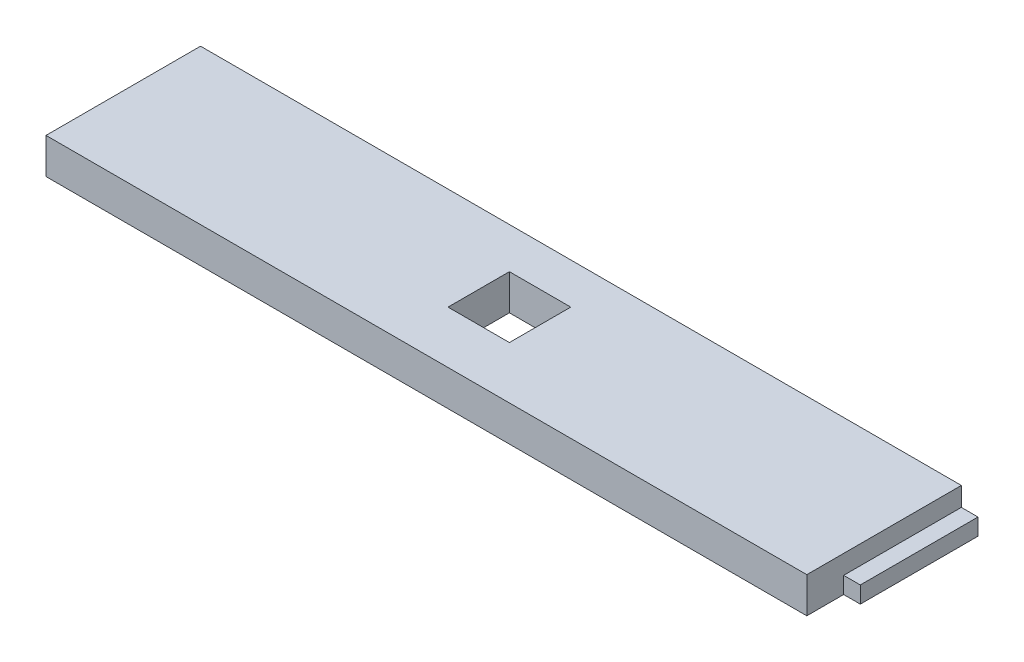
SolidWorks part; units mm, degrees
ref_plane "Front Plane" through (0, 0, 0) normal (0, 0, 1) x (1, 0, 0)
ref_plane "Top Plane" through (0, 0, 0) normal (0, 1, 0) x (1, 0, 0)
ref_plane "Right Plane" through (0, 0, 0) normal (1, 0, 0) x (0, 0, -1)
sketch "Sketch2" plane through (0, 0, 0) normal (0, 1, 0) x (1, 0, 0)
  line L0 (0, 65) -> (0, -65) construction
  line L1 (-350, -65) -> (350, -65)
  line L2 (-350, -65) -> (-350, 65)
  line L3 (-350, 65) -> (350, 65)
  line L4 (350, -65) -> (350, 65)
  line L5 (-350, -65) -> (350, 65) construction
  line L6 (-350, 65) -> (350, -65) construction
  line L7 (-320, 65) -> (-320, -65)
  line L8 (-25.815, -21) -> (25.815, -21)
  line L9 (-25.815, -21) -> (-25.815, 30.63)
  line L10 (-25.815, 30.63) -> (25.815, 30.63)
  line L11 (25.815, -21) -> (25.815, 30.63)
  line L12 (-25.815, -21) -> (25.815, 30.63) construction
  line L13 (-25.815, 30.63) -> (25.815, -21) construction
  line L14 (320, 65) -> (320, -65)
  line L15 (320, -34) -> (334, -34)
  line L16 (-315, -54.66) -> (315, -54.66)
  line L17 (-315, -54.66) -> (-315, -48.46)
  line L18 (-315, -48.46) -> (315, -48.46)
  line L19 (315, -54.66) -> (315, -48.46)
  line L20 (-320, 65) -> (-334, 65)
  line L21 (-320, 65) -> (-320, -34)
  line L22 (-320, -34) -> (-334, -34)
  line L23 (-334, 65) -> (-334, -34)
  line L24 (334, 65) -> (334, -34)
  point P0 (0, 0)
  point P8 (0, 4.815)
  dimension "D1" = 700
  dimension "D2" = 130
  dimension "D3" = 51.63
  dimension "D4" = 44
  dimension "D5" = 10.34
  dimension "D6" = 6.2
  dimension "D7" = 34.37
  dimension "D8" = 30
  dimension "D9" = 14
  dimension "D10" = 99
  dimension "D13" = 5
extrude "Boss-Extrude1" add sketch "Sketch2" along normal blind 30 contours L1 L14 L3 L7 L19 L16 L17 L18 L11 L8 L9 L10 | L16 L19 L18 L17 region at (-319.3469, 0, 49.5) region at (0, 0, 51.56)
extrude "Boss-Extrude2" add sketch "Sketch2<5>" along normal blind 14 contours L3 L23 L22 L7 | L24 L3 L14 L15 region at (-327, 0, -15.5) region at (327, 0, -15.5)
sketch "Sketch2<5>" plane through (0, 0, 0) normal (0, 1, 0) x (1, 0, 0) same geometry as "Sketch2"
